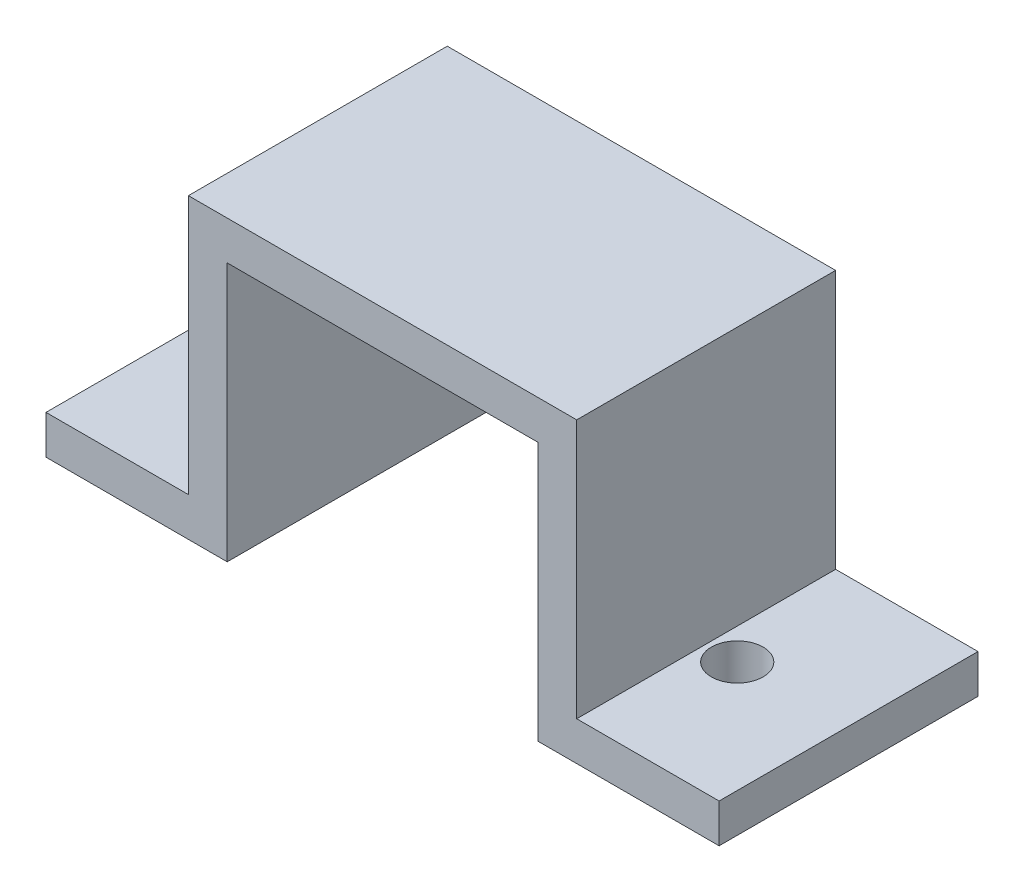
SolidWorks part; units mm, degrees
ref_plane "Front" through (0, 0, 0) normal (0, 0, 1) x (1, 0, 0)
ref_plane "Top" through (0, 0, 0) normal (0, 1, 0) x (1, 0, 0)
ref_plane "Right" through (0, 0, 0) normal (1, 0, 0) x (0, 0, -1)
sketch "草圖1" plane through (0, 0, 0) normal (0, 0, 1) x (1, 0, 0)
  line L0 (-13, -10) -> (-6, -10)
  line L1 (-6, -10) -> (-6, 0)
  line L2 (-6, 0) -> (6, 0)
  line L3 (6, 0) -> (6, -10)
  line L4 (6, -10) -> (13, -10)
  dimension "D1" = 12
  dimension "D2" = 10
  dimension "D3" = 7
  dimension "D4" = 7
  dimension "D5" = 10
extrude "伸長-薄件1" add sketch "草圖1" along normal blind 10 thin thin type one direction reverse wall 1.5
sketch "草圖2" plane through (0, -8.5, 0) normal (0, 1, 0) x (1, 0, 0)
  line L0 (8.7, -5) -> (7.5, -5) construction
  line L1 (7.5, -10) -> (7.5, 0) construction
  line L2 (-8.7, -5) -> (-7.5, -5) construction
  line L3 (-7.5, -10) -> (-7.5, 0) construction
  circle A0 centre (8.7, -5) radius 1
  circle A1 centre (-8.7, -5) radius 1
  dimension "D1" = 2
  dimension "D2" = 2
  dimension "D5" = 17.4
  dimension "D3" = 1.2
  dimension "D4" = 1.2
extrude "除料-伸長1" cut sketch "草圖2" against normal blind 10
equation "\"1。5\"=10"
